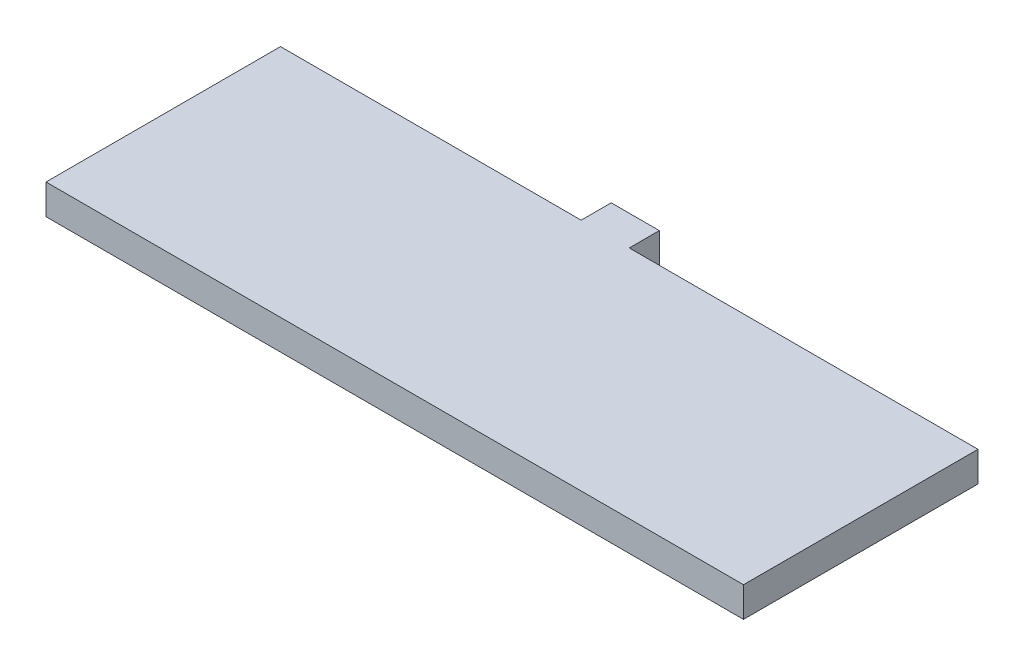
SolidWorks part; units mm, degrees
material "Acrylic (Medium-high impact)"
ref_plane "Front Plane" through (0, 0, 0) normal (0, 0, 1) x (1, 0, 0)
ref_plane "Top Plane" through (0, 0, 0) normal (0, 1, 0) x (1, 0, 0)
ref_plane "Right Plane" through (0, 0, 0) normal (1, 0, 0) x (0, 0, -1)
sketch "Sketch2" plane through (0, 0, 0) normal (0, 1, 0) x (1, 0, 0)
  line L0 (-26.8097, 0) -> (-26.8097, -24.765) construction
  line L1 (-36.83, 0) -> (36.83, 0)
  line L2 (-36.83, 0) -> (-36.83, -24.765)
  line L3 (-36.83, -24.765) -> (36.83, -24.765)
  line L4 (36.83, 0) -> (36.83, -24.765)
  line L5 (-5.08, 0) -> (0, 0)
  line L6 (-5.08, 0) -> (-5.08, 3.175)
  line L7 (-5.08, 3.175) -> (0, 3.175)
  line L8 (0, 0) -> (0, 3.175)
  line L9 (29.9847, 0) -> (29.9847, -24.765) construction
  line L10 (0, 0) -> (0, 3.175) construction
  line L11 (0, 3.175) -> (6.477, 3.175) construction
  line L12 (6.477, 3.175) -> (6.477, 0) construction
  point P8 (0, -24.765)
  point P14 (6.477, 1.5875)
  dimension "D1" = 73.66
  dimension "D2" = 56.7944
  dimension "D3" = 5.08
  dimension "D4" = 27.94
  dimension "D7" = 6.477
  dimension "D8" = 3.175
  dimension "D6" = 23.5077
extrude "Boss-Extrude1" add sketch "Sketch2" along normal blind 3.175 contours L4 L1 L2 L3 | L1 L8 L7 L6 region at (0, 0, 12.3825) region at (-2.54, 0, -1.5875)
equation "\"bottomThickness\"= .25in"
equation "\"wallThickness\"= .125in"
equation "\"D8@Sketch2\"=\"wallThickness\""
equation "\"D1@Boss-Extrude1\"=\"wallThickness\""
